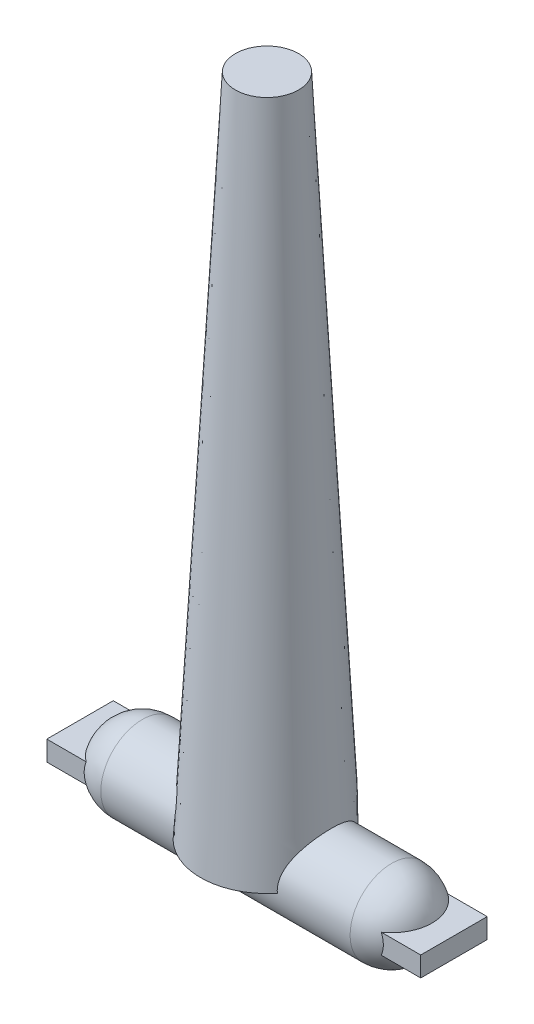
SolidWorks part; units mm, degrees
material "ABS"
ref_plane "Front" through (0, 0, 0) normal (0, 0, 1) x (1, 0, 0)
ref_plane "Top" through (0, 0, 0) normal (0, 1, 0) x (1, 0, 0)
ref_plane "Right" through (0, 0, 0) normal (1, 0, 0) x (0, 0, -1)
sketch "Sketch1" plane through (0, 0, 0) normal (0, 0, 1) x (1, 0, 0)
  line L0 (0, 50.8) -> (0, 0)
  line L1 (0, 0) -> (5.0753, 0)
  line L2 (5.0753, 0) -> (2.413, 50.8)
  line L3 (2.413, 50.8) -> (0, 50.8)
  dimension "D1" = 2.413
  dimension "D2" = 3
  dimension "D3" = 50.8
revolve "Revolve1" add sketch "Sketch1" angle 360 about L0
sketch "Sketch3" plane through (0, 0, 0) normal (1, 0, 0) x (0, 0, -1)
  circle A0 centre (0, 0) radius 3.175
  dimension "D1" = 6.35
extrude "Boss-Extrude1" add sketch "Sketch3" along normal mid plane 25.4
fillet "Fillet1" radius 3.175 2 edges at (-12.7, 0, -3.175) (12.7, 0, -3.175)
sketch "Sketch4" plane through (0, 0, 0) normal (1, 0, 0) x (0, 0, -1)
  line L1 (-2.54, 0.762) -> (2.54, 0.762)
  line L2 (-2.54, 0.762) -> (-2.54, -0.762)
  line L3 (-2.54, -0.762) -> (2.54, -0.762)
  line L4 (2.54, 0.762) -> (2.54, -0.762)
  point P4 (-2.54, 0)
  point P6 (0, 0.762)
  dimension "D1" = 5.08
  dimension "D2" = 1.524
extrude "Boss-Extrude2" add sketch "Sketch4" along normal mid plane 28.575
